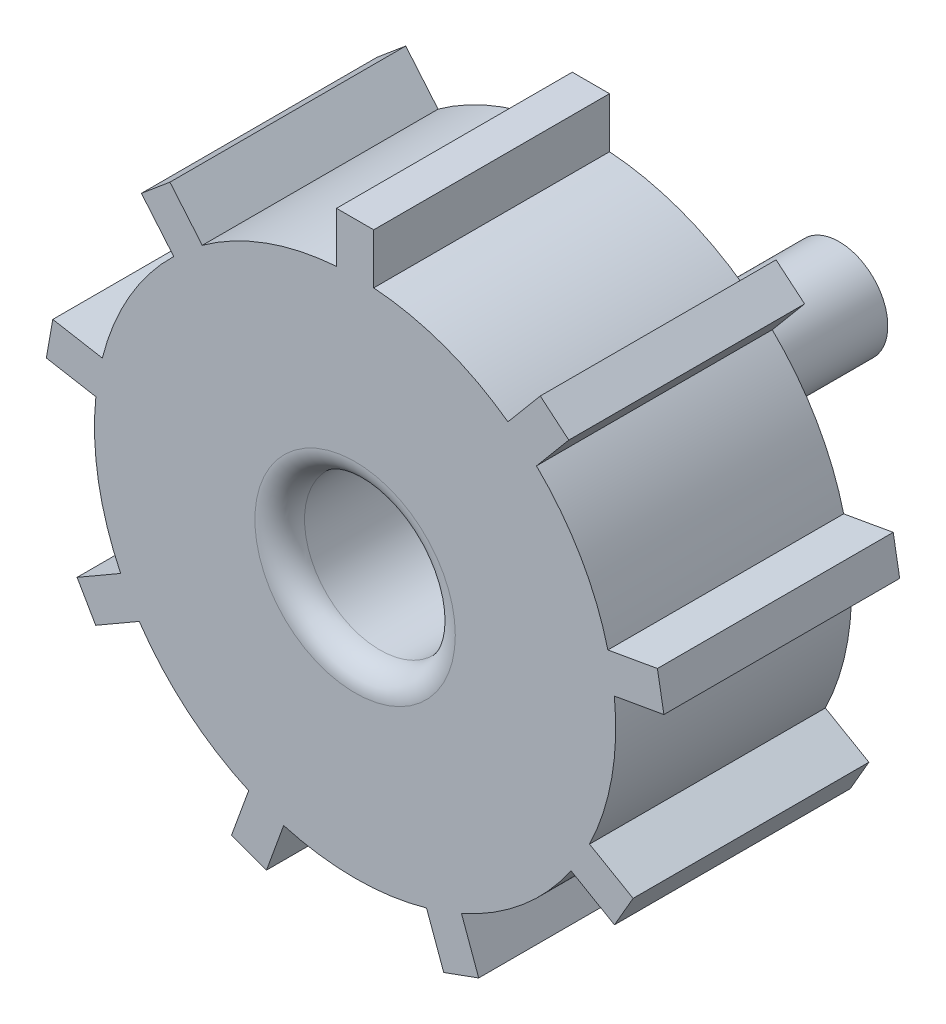
SolidWorks part; units mm, degrees
ref_plane "Ebene vorne" through (0, 0, 0) normal (0, 0, 1) x (1, 0, 0)
ref_plane "Ebene oben" through (0, 0, 0) normal (0, 1, 0) x (1, 0, 0)
ref_plane "Ebene rechts" through (0, 0, 0) normal (1, 0, 0) x (0, 0, -1)
sketch "Skizze1" plane through (0, 0, 0) normal (0, 0, 1) x (1, 0, 0)
  circle A0 centre (0, 0) radius 6
  dimension "D1" = 12
extrude "Aufsatz-Linear austragen1" add sketch "Skizze1" along normal blind 9
sketch "Skizze2" plane through (0, 0, 0) normal (0, 0, -1) x (-1, 0, 0)
  circle A0 centre (0, 0) radius 3.925
  dimension "D1" = 7.85
extrude "Aufsatz-Linear austragen2" add sketch "Skizze2" along normal blind 11
sketch "Skizze3" plane through (0, 0, 9) normal (0, 0, 1) x (1, 0, 0)
  circle A0 centre (0, 0) radius 21
  dimension "D1" = 42
extrude "Aufsatz-Linear austragen3" add sketch "Skizze3" along normal blind 19
sketch "Skizze4" plane through (0, 0, 28) normal (0, 0, 1) x (1, 0, 0)
  circle A0 centre (0, 0) radius 6.075
  dimension "D1" = 12.15
extrude "Schnitt-Linear austragen2" cut sketch "Skizze4" against normal blind 10
fillet "Verrundung1" radius 2 1 edges at (6.075, 0, 28)
sketch "Skizze6" plane through (0, 0, 28) normal (0, 0, 1) x (1, 0, 0)
  line L0 (0, 0) -> (0, 21) construction
  line L1 (0, 21) -> (0, 25) construction
  line L2 (-1.5, 25) -> (1.5, 25)
  line L3 (-1.5, 25) -> (-1.5, 20.9464)
  line L4 (1.5, 25) -> (1.5, 20.9464)
  circle A0 centre (0, 0) radius 21
  point P8 (0, 25)
  circle M3 centre (0, 0) radius 8.075
  circle M4 centre (0, 0) radius 21
  dimension "D2" = 42
  dimension "D1" = 4
  dimension "D3" = 3
extrude "Aufsatz-Linear austragen4" add sketch "Skizze6" against normal up to surface (19 mm away) contours L4 L2 L3 M4 | M4 M3 region at (0, 22.991, 28) region at (0, 20.406, 28) up to face at (6, 0, 9)
pattern_circular "Kreismuster1" count 9 over 360 about axis through (0, 0, 28) along (0, 0, -1) of "Aufsatz-Linear austragen4" reverse direction yes
